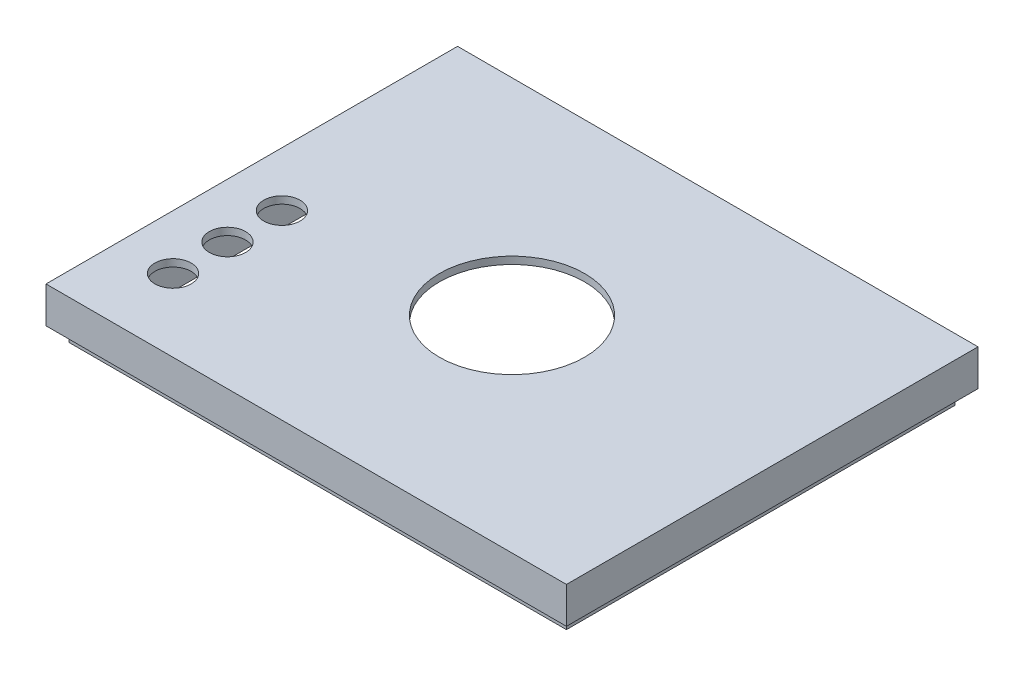
SolidWorks part; units mm, degrees
ref_plane "Front Plane" through (0, 0, 0) normal (0, 0, 1) x (1, 0, 0)
ref_plane "Top Plane" through (0, 0, 0) normal (0, 1, 0) x (1, 0, 0)
ref_plane "Right Plane" through (0, 0, 0) normal (1, 0, 0) x (0, 0, -1)
sketch "Sketch1" plane through (0, 0, 0) normal (0, 1, 0) x (1, 0, 0)
  line L1 (-24.505, -34.562) -> (47.195, -34.562)
  line L2 (-24.505, -34.562) -> (-24.505, 22.138)
  line L3 (-24.505, 22.138) -> (47.195, 22.138)
  line L4 (47.195, -34.562) -> (47.195, 22.138)
  dimension "D1" = 71.7
  dimension "D2" = 56.7
extrude "Boss-Extrude1" add sketch "Sketch1" along normal blind 5
sketch "Sketch2" plane through (0, 0, 0) normal (0, -1, 0) x (1, 0, 0)
  line L0 (-24.505, -22.138) -> (-24.505, 34.562) construction
  line L1 (-22.905, 32.962) -> (45.595, 32.962)
  line L2 (-22.905, 32.962) -> (-22.905, -20.538)
  line L3 (-22.905, -20.538) -> (45.595, -20.538)
  line L4 (45.595, 32.962) -> (45.595, -20.538)
  line L5 (-21.905, 31.962) -> (44.595, 31.962)
  line L6 (-21.905, 31.962) -> (-21.905, -19.538)
  line L7 (-21.905, -19.538) -> (44.595, -19.538)
  line L8 (44.595, 31.962) -> (44.595, -19.538)
  line L9 (47.195, -22.138) -> (-24.505, -22.138) construction
  dimension "D1" = 53.5
  dimension "D2" = 68.5
  dimension "D3" = 1.6
  dimension "D4" = 1.6
  dimension "D5" = 1
  dimension "D6" = 1
  dimension "D7" = 1
  dimension "D8" = 1
extrude "Boss-Extrude2" add sketch "Sketch2" along normal blind 2
extrude "Cut-Extrude1" cut sketch "Sketch2<2>" against normal blind 4 contours L8 L5 L6 L7 region at (11.345, 0, 6.212)
sketch "Sketch2<2>" plane through (0, 0, 0) normal (0, -1, 0) x (1, 0, 0) same geometry as "Sketch2"
sketch "Sketch3" plane through (0, 5, 0) normal (0, 1, 0) x (1, 0, 0)
  line L0 (47.195, -34.562) -> (47.195, 22.138) construction
  line L1 (47.195, 22.138) -> (-24.505, 22.138) construction
  line L2 (-24.505, -34.562) -> (47.195, -34.562) construction
  line L3 (-24.505, 22.138) -> (-24.505, -34.562) construction
  circle A0 centre (-17.005, -24.562) radius 2.5
  circle A1 centre (-17.005, -17.062) radius 2.5
  circle A2 centre (-17.005, -9.562) radius 2.5
  circle A3 centre (11.345, -6.212) radius 10
  point P8 (47.195, -6.212)
  point P11 (11.345, 22.138)
  dimension "D1" = 20
  dimension "D2" = 0
  dimension "D3" = 0
  dimension "D4" = 5
  dimension "D5" = 5
  dimension "D6" = 5
  dimension "D7" = 10
  dimension "D8" = 7.5
  dimension "D9" = 7.5
  dimension "D10" = 7.5
  dimension "D11" = 7.5
  dimension "D12" = 7.5
extrude "Cut-Extrude2" cut sketch "Sketch3" against normal blind 1
